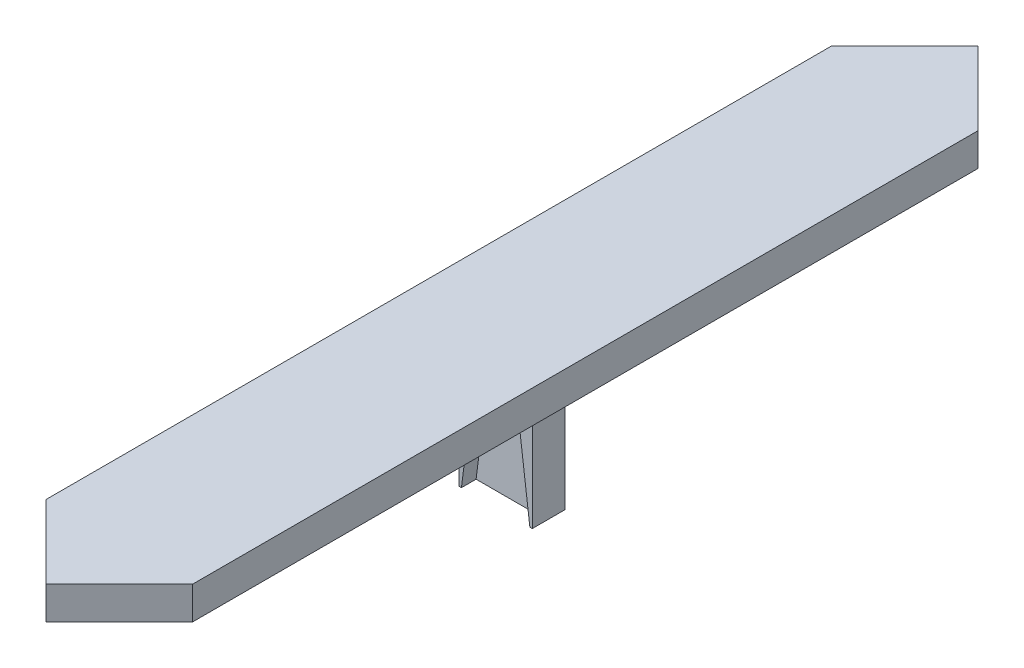
SolidWorks part; units mm, degrees
ref_plane "Front Plane" through (0, 0, 0) normal (0, 0, 1) x (1, 0, 0)
ref_plane "Top Plane" through (0, 0, 0) normal (0, 1, 0) x (1, 0, 0)
ref_plane "Right Plane" through (0, 0, 0) normal (1, 0, 0) x (0, 0, -1)
sketch "Sketch1" plane through (0, 0, 0) normal (0, 1, 0) x (1, 0, 0)
  line L0 (0, 5) -> (0, -13) construction
  line L1 (0, 0) -> (7, -7)
  line L2 (7, -7) -> (7, -82)
  line L3 (7, -82) -> (0, -89)
  line L4 (-7, -82) -> (0, -89)
  line L5 (-7, -7) -> (-7, -82)
  line L6 (0, 0) -> (-7, -7)
  point P5 (0, 0)
  point P8 (0, 0)
  point P11 (0, 0)
  point P12 (0, 0)
  dimension "D1" = 135
  dimension "D2" = 135
  dimension "D4" = 75
  dimension "D3" = 14
  dimension "D5" = 0
extrude "Boss-Extrude1" add sketch "Sketch1" along normal blind 3.125
sketch "Sketch2" plane through (0, 0, 0) normal (0, -1, 0) x (1, 0, 0)
  line L0 (0, 0) -> (0, 89) construction
  line L1 (3.5, 42.9375) -> (-3.5, 42.9375)
  line L2 (3.5, 42.9375) -> (3.5, 46.0625)
  line L3 (3.5, 46.0625) -> (-3.5, 46.0625)
  line L4 (-3.5, 42.9375) -> (-3.5, 46.0625)
  line L5 (3.5, 42.9375) -> (-3.5, 46.0625) construction
  line L6 (3.5, 46.0625) -> (-3.5, 42.9375) construction
  line L7 (7, 44.5) -> (-7, 44.5) construction
  line L8 (7, 82) -> (7, 7) construction
  line L9 (-7, 7) -> (-7, 82) construction
  point P0 (0, 44.5)
  dimension "D1" = 7
  dimension "D2" = 0
  dimension "D3" = 3.125
  dimension "D4" = 0
extrude "Boss-Extrude2" add sketch "Sketch2" along normal blind 12
sketch "Sketch3" plane through (0, 0, 46.0625) normal (0, 0, 1) x (1, 0, 0)
  line L0 (0, -12) -> (0, 0) construction
  line L1 (3.5, -12) -> (-3.5, -12) construction
  line L2 (3.5, 0) -> (-3.5, 0) construction
  line L3 (3.5, -13.84) -> (-3.5, -13.84)
  line L8 (3.5, -12) -> (3.5, 0) construction
  line L9 (-3.5, -12) -> (-3.5, 0) construction
  line L10 (2, -2) -> (3.5, -13.84)
  line L11 (-2, -2) -> (-3.5, -13.84)
  arc A0 (2, -2) -> (-2, -2) centre (0, -2) ccw
  point P6 (0, -6)
  dimension "D1" = 4
  dimension "D2" = 11.84
  dimension "D3" = 2
extrude "Cut-Extrude1" cut sketch "Sketch3" against normal blind 1.4
equation "\"D2@Sketch1\"=\"D1@Sketch1\""
